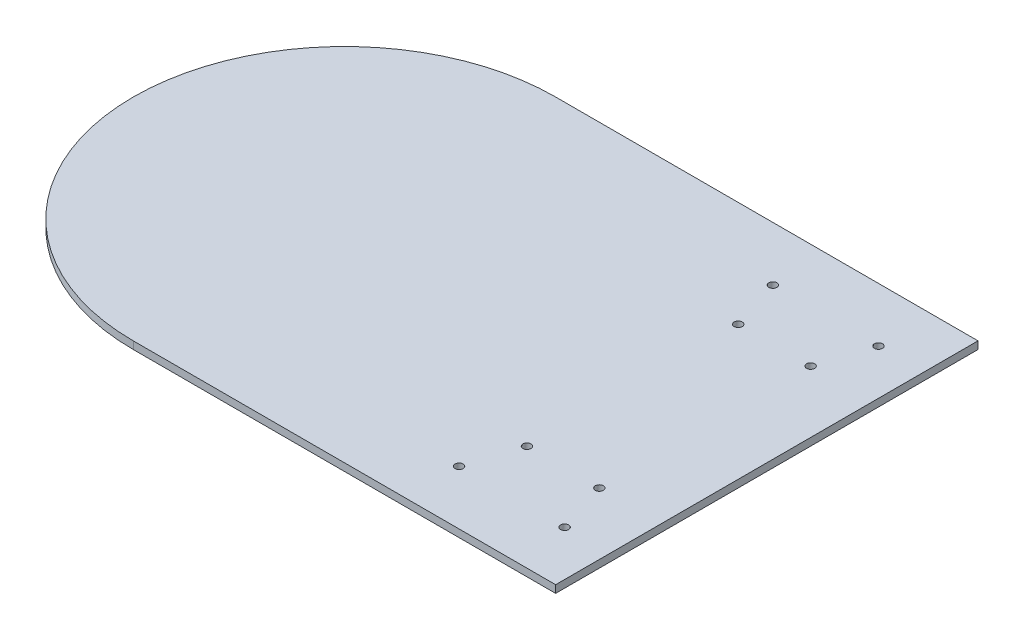
SolidWorks part; units mm, degrees
material "Acrylic (Medium-high impact)"
ref_plane "Front Plane" through (0, 0, 0) normal (0, 0, 1) x (1, 0, 0)
ref_plane "Top Plane" through (0, 0, 0) normal (0, 1, 0) x (1, 0, 0)
ref_plane "Right Plane" through (0, 0, 0) normal (1, 0, 0) x (0, 0, -1)
sketch "Sketch2" plane through (0, 0, 0) normal (0, 1, 0) x (1, 0, 0)
  line L0 (0, 0) -> (0, 177.8)
  line L1 (0, 177.8) -> (-177.8, 177.8)
  line L2 (0, 0) -> (-177.8, 0)
  line L3 (-177.8, 177.8) -> (-177.8, 0) construction
  arc A0 (-177.8, 177.8) -> (-177.8, 0) centre (-177.8, 88.9) ccw
  dimension "D1" = 177.8
  dimension "D2" = 177.8
extrude "Boss-Extrude1" add sketch "Sketch2" along normal blind 3.175
sketch "Motor Mount Hole Locations" plane through (0, 0, 0) normal (0, 1, 0) x (1, 0, 0)
  line L0 (0, 0) -> (0, 177.8) construction
  line L6 (0, 88.9) -> (-266.7, 88.9) construction
  line L11 (-63.5, 154.9552) -> (-19.05, 154.9552) construction
  line L12 (-56.515, 133.3652) -> (-26.035, 133.3652) construction
  line L13 (-41.275, 133.3652) -> (-41.275, 154.9552) construction
  line L14 (0, 177.8) -> (-177.8, 177.8) construction
  line L15 (-56.515, 44.4348) -> (-26.035, 44.4348) construction
  line L16 (-41.275, 44.4348) -> (-41.275, 22.8448) construction
  line L17 (-63.5, 22.8448) -> (-19.05, 22.8448) construction
  arc A0 (-177.8, 177.8) -> (-177.8, 0) centre (-177.8, 88.9) ccw construction
  dimension "D1" = 21.59
  dimension "D2" = 44.45
  dimension "D3" = 30.48
  dimension "D4" = 22.8448
  dimension "D5" = 19.05
hole_wizard "M3 Clearance Hole1" positions "Sketch3" profile "Sketch4" hole size "M3" standard "ANSI Metric" end condition through all
sketch "Sketch3" plane through (0, 3.175, 0) normal (0, 1, 0) x (1, 0, 0)
  point P0 (-63.5, 154.9552)
  point P3 (-19.05, 154.9552)
  point P6 (-56.515, 133.3652)
  point P9 (-26.035, 133.3652)
  point P12 (-56.515, 44.4348)
  point P15 (-26.035, 44.4348)
  point P18 (-63.5, 22.8448)
  point P21 (-19.05, 22.8448)
sketch "Sketch4" plane through (-63.5, 3.175, -154.9552) normal (1, 0, 0) x (0, 0, 1)
  line L0 (0, 0) -> (0, 3.175)
  line L1 (0, 3.175) -> (1.7, 3.175)
  line L2 (1.7, 3.175) -> (1.7, 0)
  line L5 (1.7, 0) -> (0, 0)
  line L11 (0, -6.35) -> (0, 107.95) construction
  dimension "Thru Hole Dia." = 3.4
  dimension "Thru Hole Depth" = 3.175
